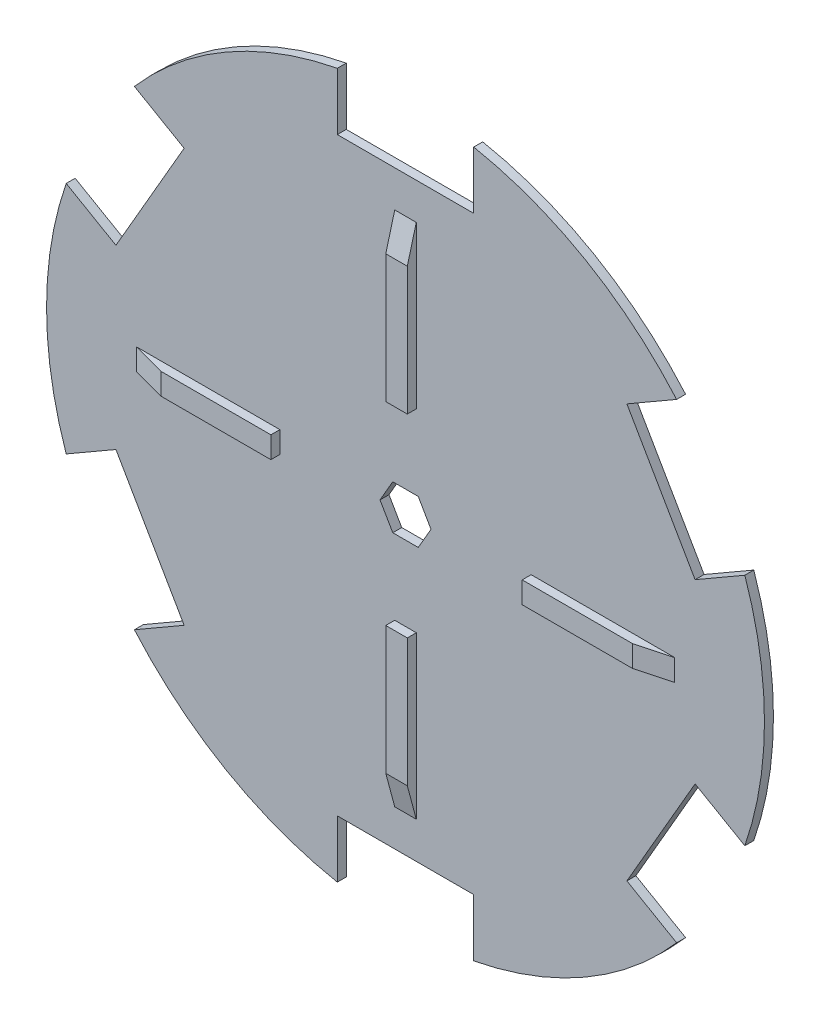
SolidWorks part; units mm, degrees
ref_plane "Front Plane" through (0, 0, 0) normal (0, 0, 1) x (1, 0, 0)
ref_plane "Top Plane" through (0, 0, 0) normal (0, 1, 0) x (1, 0, 0)
ref_plane "Right Plane" through (0, 0, 0) normal (1, 0, 0) x (0, 0, -1)
sketch "Sketch1" plane through (0, 0, 0) normal (0, 0, 1) x (1, 0, 0)
  circle A0 centre (0, 0) radius 100
  dimension "D1" = 200
extrude "Boss-Extrude1" add sketch "Sketch1" along normal blind 2.5 contours A0
sketch "Sketch8" plane through (0, 0, 0) normal (0, 0, -1) x (-1, 0, 0)
  text T0 "02-04-141118"
extrude "Cut-Extrude6" cut sketch "Sketch8" against normal blind 0.2
sketch "Sketch9" plane through (0, 0, 2.5) normal (0, 0, 1) x (1, 0, 0)
  line L1 (-7.1014, 0) -> (-3.5507, -6.15)
  line L2 (-3.5507, -6.15) -> (3.5507, -6.15)
  line L3 (3.5507, -6.15) -> (7.1014, 0)
  line L4 (7.1014, 0) -> (3.5507, 6.15)
  line L5 (3.5507, 6.15) -> (-3.5507, 6.15)
  line L6 (-3.5507, 6.15) -> (-7.1014, 0)
  circle A0 centre (0, 0) radius 6.15 construction
  dimension "D1" = 12.3
extrude "Cut-Extrude7" cut sketch "Sketch9" against normal blind 10
sketch "Sketch11" plane through (0, 0, 2.5) normal (0, 0, 1) x (1, 0, 0)
  line L0 (0, 0) -> (-75, 0)
  line L1 (-75, 0) -> (-75, 3)
  line L2 (-75, 3) -> (-35, 3)
  line L3 (-35, 3) -> (-35, -3)
  line L4 (-35, -3) -> (-75, -3)
  line L5 (-75, -3) -> (-75, 0)
  line L6 (0, 0) -> (0, 72)
  line L7 (0, 72) -> (-3, 72)
  line L8 (-3, 72) -> (-3, 27)
  line L9 (-3, 27) -> (3, 27)
  line L10 (3, 27) -> (3, 72)
  line L11 (3, 72) -> (0, 72)
  line L12 (35, 3) -> (75, 3)
  line L13 (35, -3) -> (35, 3)
  line L14 (75, -3) -> (35, -3)
  line L15 (75, 3) -> (75, 0)
  line L16 (75, 0) -> (75, -3)
  line L17 (3, -27) -> (-3, -27)
  line L18 (3, -72) -> (3, -27)
  line L19 (-3, -27) -> (-3, -72)
  line L20 (0, -72) -> (3, -72)
  line L21 (-3, -72) -> (0, -72)
  point P20 (0, 0)
  point P26 (0, 0)
  dimension "D1" = 3
  dimension "D2" = 6
  dimension "D3" = 6
  dimension "D4" = 3
  dimension "D5" = 75
  dimension "D6" = 40
  dimension "D7" = 72
  dimension "D8" = 45
  dimension "D9" = 2
  dimension "D10" = 2
extrude "Boss-Extrude2" add sketch "Sketch11" along normal blind 2.5 contours L7 L8 L9 L10 L11 | L1 L2 L3 L4 L5 | L14 L13 L12 L15 L16 | L19 L21 L20 L18 L17
chamfer "Chamfer1" distance 2.5 angle 75 4 edges at (75, 0, 5) (0, 72, 5) (0, -72, 5) (-75, 0, 5)
sketch "Sketch12" plane through (0, 0, 2.5) normal (0, 0, 1) x (1, 0, 0)
  line L0 (80.6686, 24.6347) -> (94.525, 32.6347)
  line L1 (0, 82.1784) -> (19, 82.1784)
  line L2 (19, 82.1784) -> (19, 98.1784)
  line L3 (0, 82.1784) -> (-19, 82.1784)
  line L4 (-19, 82.1784) -> (-19, 98.1784)
  line L5 (71.1686, 41.0892) -> (80.6686, 24.6347)
  line L6 (61.6686, 57.5437) -> (75.525, 65.5437)
  line L7 (71.1686, 41.0892) -> (61.6686, 57.5437)
  line L8 (61.6686, -57.5437) -> (75.525, -65.5437)
  line L9 (71.1686, -41.0892) -> (61.6686, -57.5437)
  line L10 (80.6686, -24.6347) -> (94.525, -32.6347)
  line L11 (71.1686, -41.0892) -> (80.6686, -24.6347)
  line L12 (-19, -82.1784) -> (-19, -98.1784)
  line L13 (0, -82.1784) -> (-19, -82.1784)
  line L14 (19, -82.1784) -> (19, -98.1784)
  line L15 (0, -82.1784) -> (19, -82.1784)
  line L16 (-80.6686, -24.6347) -> (-94.525, -32.6347)
  line L17 (-71.1686, -41.0892) -> (-80.6686, -24.6347)
  line L18 (-61.6686, -57.5437) -> (-75.525, -65.5437)
  line L19 (-71.1686, -41.0892) -> (-61.6686, -57.5437)
  line L20 (-61.6686, 57.5437) -> (-75.525, 65.5437)
  line L21 (-71.1686, 41.0892) -> (-61.6686, 57.5437)
  line L22 (-80.6686, 24.6347) -> (-94.525, 32.6347)
  line L23 (-71.1686, 41.0892) -> (-80.6686, 24.6347)
  arc A0 (19, 98.1784) -> (-19, 98.1784) centre (0, 0) ccw
  arc A1 (94.525, 32.6347) -> (75.525, 65.5437) centre (0, 0) ccw
  arc A2 (75.525, -65.5437) -> (94.525, -32.6347) centre (0, 0) ccw
  arc A3 (-19, -98.1784) -> (19, -98.1784) centre (0, 0) ccw
  arc A4 (-94.525, -32.6347) -> (-75.525, -65.5437) centre (0, 0) ccw
  arc A5 (-75.525, 65.5437) -> (-94.525, 32.6347) centre (0, 0) ccw
  point P36 (0, 0)
  dimension "D1" = 200
  dimension "D2" = 19
  dimension "D3" = 19
  dimension "D4" = 16
  dimension "D5" = 6
extrude "Cut-Extrude8" cut sketch "Sketch12" against normal blind 10
equation "\"1.5.00mm\"=3"
